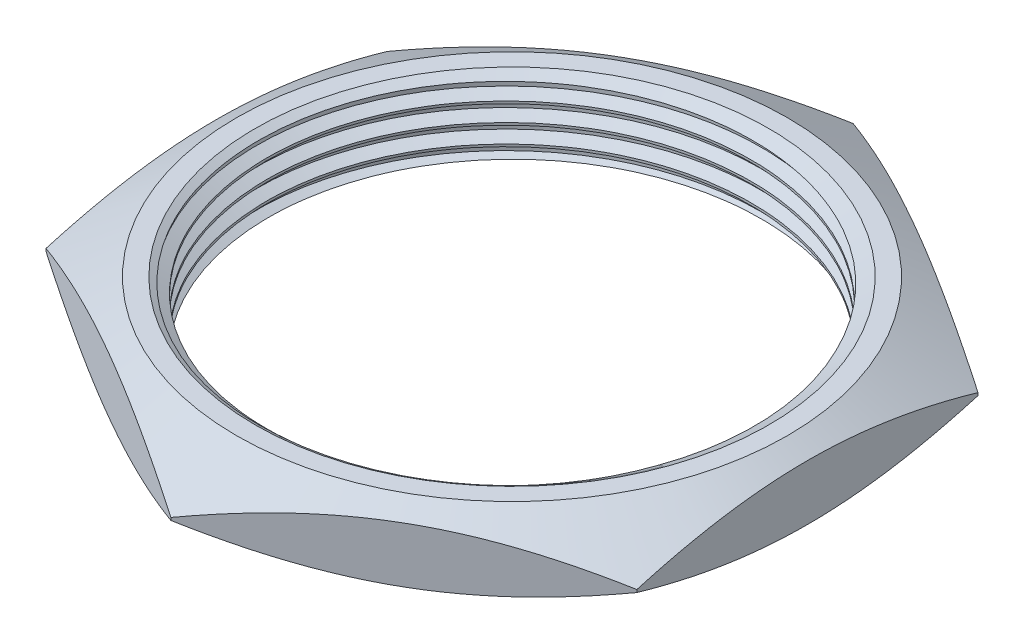
SolidWorks part; units mm, degrees
material "Легированная сталь"
ref_plane "Спереди" through (0, 0, 0) normal (0, 0, 1) x (1, 0, 0)
ref_plane "Сверху" through (0, 0, 0) normal (0, 1, 0) x (1, 0, 0)
ref_plane "Справа" through (0, 0, 0) normal (1, 0, 0) x (0, 0, -1)
sketch "Эскиз1" plane through (0, 0, 0) normal (0, 1, 0) x (1, 0, 0)
  line L1 (11.1, 6.4086) -> (0, 12.8172)
  line L2 (0, 12.8172) -> (-11.1, 6.4086)
  line L3 (-11.1, 6.4086) -> (-11.1, -6.4086)
  line L4 (-11.1, -6.4086) -> (0, -12.8172)
  line L5 (0, -12.8172) -> (11.1, -6.4086)
  line L6 (11.1, -6.4086) -> (11.1, 6.4086)
  circle A0 centre (0, 0) radius 11.1 construction
  circle A1 centre (0, 0) radius 9.1
  dimension "D2" = 18.2
  dimension "D1" = 22.2
extrude "Бобышка-Вытянуть1" add sketch "Эскиз1" along normal mid plane 2.95
sketch "Эскиз3" plane through (0, 0, 0) normal (-1, 0, 0) x (0, 0, 1)
  line L0 (17.0084, 0) -> (-24.3659, 0) construction
  line L1 (0, 8.0817) -> (0, -8.5445) construction
  line L2 (12.8172, 0.05) -> (13.349, 0.05)
  line L3 (10.349, 3.05) -> (13.349, 3.05)
  line L4 (10.349, 3.05) -> (10.349, 1.475)
  line L5 (10.349, 1.475) -> (12.8172, 0.05)
  line L6 (13.349, 3.05) -> (13.349, 0.05)
  line L7 (10.349, -1.475) -> (12.8172, -0.05)
  line L8 (10.349, -1.475) -> (10.349, -3.05)
  line L9 (10.349, -3.05) -> (13.349, -3.05)
  line L10 (13.349, -0.05) -> (13.349, -3.05)
  line L11 (12.8172, -0.05) -> (13.349, -0.05)
  line L15 (12.8172, 1.475) -> (6.4086, 1.475) construction
  line L16 (12.8172, -1.475) -> (6.4086, -1.475) construction
  line L17 (12.8172, 1.475) -> (12.8172, -1.475) construction
  line L18 (9.649, 2.075) -> (9.649, 1.475)
  line L19 (9.649, 1.475) -> (9.049, 1.1286)
  line L20 (9.049, 1.1286) -> (9.049, 2.075)
  line L21 (9.049, 2.075) -> (9.649, 2.075)
  line L22 (9.649, -2.075) -> (9.649, -1.475)
  line L23 (9.649, -1.475) -> (9.049, -1.1286)
  line L24 (9.049, -1.1286) -> (9.049, -2.075)
  line L25 (9.049, -2.075) -> (9.649, -2.075)
  point P19 (9.0998, 1.1413)
  point P22 (0, 0)
  point P23 (0, 0)
  point P24 (9.0706, 1.1201)
  dimension "D1" = 3
  dimension "D2" = 0.1
  dimension "D3" = 30
  dimension "D4" = 60
  dimension "D5" = 0.6
  dimension "D6" = 0.7
revolve "Вырез-Повернуть1" cut sketch "Эскиз3" angle 360 about L1
thread "Резьба1" pitch 0.7 method cut profile "Профиль резьбы1" start angle 0, offset 1, length 0, pitch 0.7, diameter 18.2
ref_plane "Плоскость2" through (-9.1, 2.158, 0) normal (0, 0, -1) x (1, 0, 0)
sketch "Профиль резьбы1" plane through (-9.1, 2.158, 0) normal (0, 0, -1) x (1, 0, 0)
  line L0 (0, 0) -> (0, 0.7) construction
  line L11 (0, 0) -> (0, 0.6125)
  line L12 (0, 0.6125) -> (-0.3789, 0.3937)
  line L13 (-0.3789, 0.3937) -> (-0.3789, 0.2187)
  line L15 (-0.3789, 0.2187) -> (0, 0)
  line L17 (-0.3789, 0.3062) -> (0, 0.3062) construction
  point P2 (0, 0)
  dimension "Pitch" = 0.7
  dimension "Profile_Angle" = 60
  dimension "Profile_Land" = 0.175
  dimension "Profile_Height" = 0.3789
